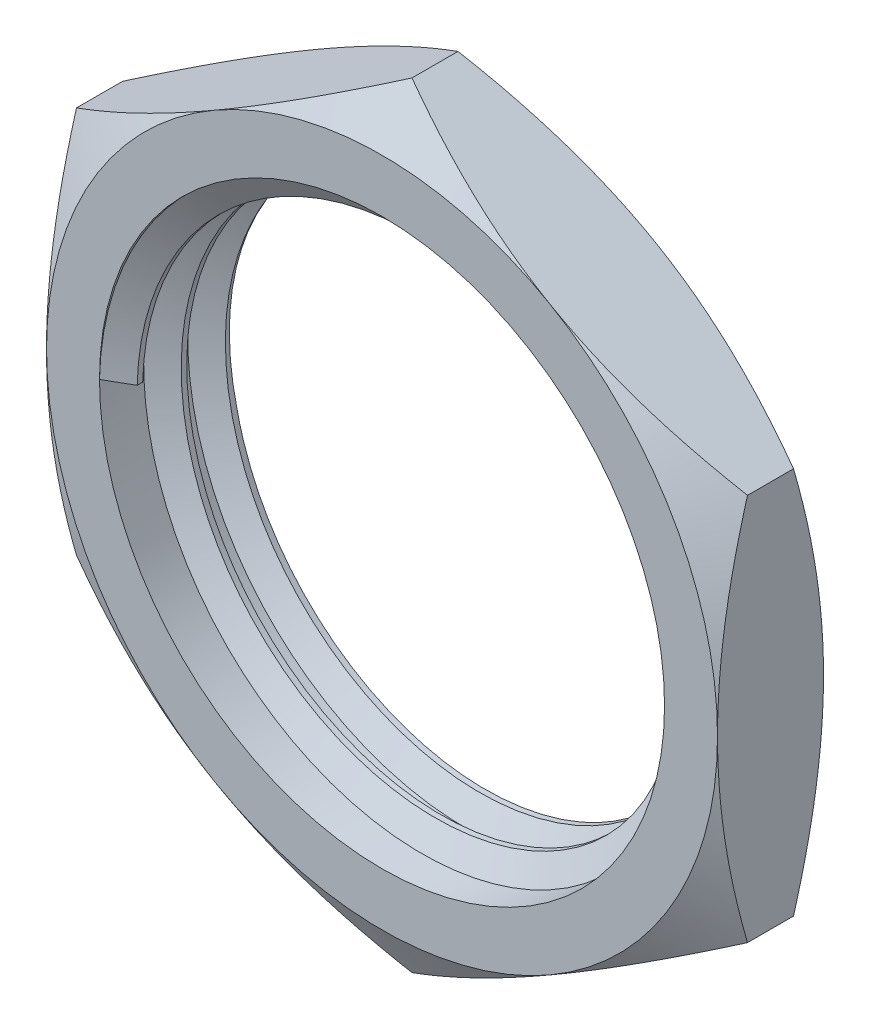
SolidWorks part; units mm, degrees
ref_plane "Front Plane" through (0, 0, 0) normal (0, 0, 1) x (1, 0, 0)
ref_plane "Top Plane" through (0, 0, 0) normal (0, 1, 0) x (1, 0, 0)
ref_plane "Right Plane" through (0, 0, 0) normal (1, 0, 0) x (0, 0, -1)
sketch "Sketch2" plane through (0, 0, 0) normal (0, 0, 1) x (1, 0, 0)
  line L1 (0, 10.9697) -> (-9.5, 5.4848)
  line L2 (-9.5, 5.4848) -> (-9.5, -5.4848)
  line L3 (-9.5, -5.4848) -> (0, -10.9697)
  line L4 (0, -10.9697) -> (9.5, -5.4848)
  line L5 (9.5, -5.4848) -> (9.5, 5.4848)
  line L6 (9.5, 5.4848) -> (0, 10.9697)
  circle A0 centre (0, 0) radius 9.5 construction
  circle A1 centre (0, 0) radius 8
  dimension "D2" = 16
  dimension "D1" = 19
extrude "Boss-Extrude1" add sketch "Sketch2" along normal blind 3
sketch "Sketch3" plane through (0, 0, 3) normal (0, 0, 1) x (1, 0, 0)
  line L0 (0, 10.9697) -> (-9.5, 5.4848) construction
  circle A0 centre (0, 0) radius 9.5
extrude "Cut-Extrude1" cut sketch "Sketch3" against normal blind 3 draft 60 flip side to cut
sketch "Sketch4" plane through (0, 0, 0) normal (0, 0, -1) x (-1, 0, 0)
  line L0 (-9.5, 5.4848) -> (0, 10.9697) construction
  circle A0 centre (0, 0) radius 9.5
extrude "Cut-Extrude2" cut sketch "Sketch4" against normal blind 3 draft 60 flip side to cut
thread "Thread1" pitch 1.25 method extrude trim with end face yes profile "Thread Profile1" start angle 0, offset 0, length 4, pitch 1.25, diameter 16
ref_plane "Plane1" through (-8, 0, 3) normal (0, 1, 0) x (1, 0, 0)
sketch "Thread Profile1" plane through (-8, 0, 3) normal (0, 1, 0) x (1, 0, 0)
  line L0 (0, 0) -> (0, 1.25) construction
  line L1 (0, 0) -> (0.6766, 0.3906)
  line L2 (0.6766, 0.3906) -> (0.6766, 0.5469)
  line L3 (0.6766, 0.5469) -> (0, 0.9375)
  line L4 (0.6766, 0.4687) -> (0, 0.4687) construction
  line L11 (0, 0) -> (0, 0.9375)
  point P2 (0, 0)
  dimension "Pitch" = 1.25
  dimension "Profile_Angle" = 60
  dimension "Profile_Land" = 0.1562
  dimension "Profile_Height" = 0.6766
